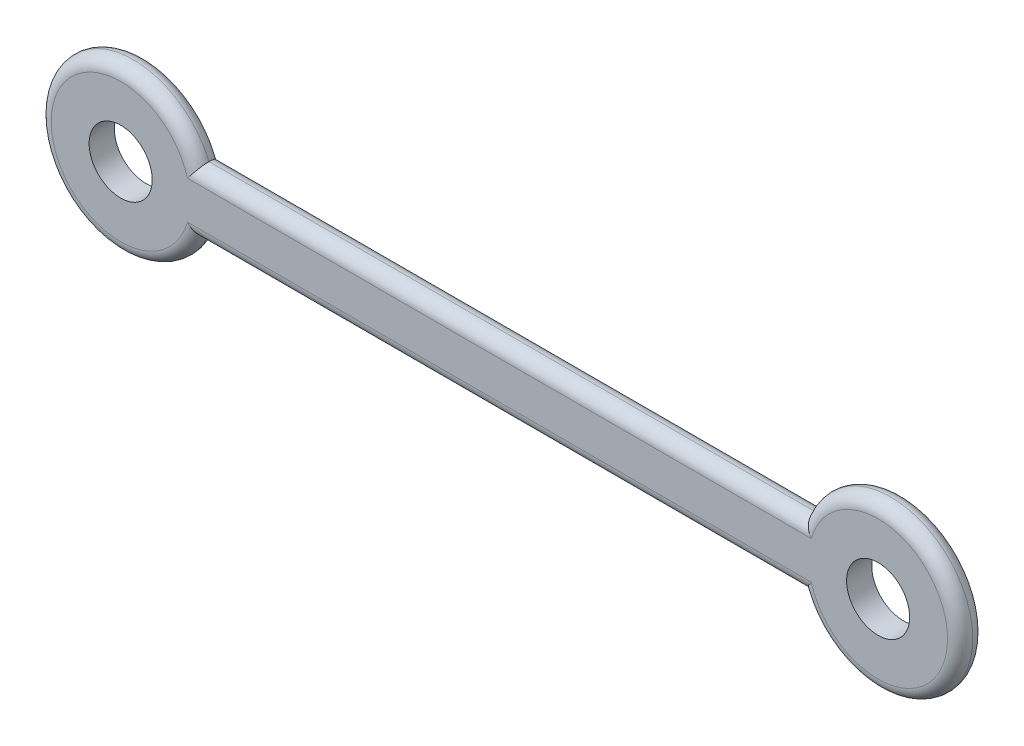
SolidWorks part; units mm, degrees
ref_plane "Front Plane" through (0, 0, 0) normal (0, 0, 1) x (1, 0, 0)
ref_plane "Top Plane" through (0, 0, 0) normal (0, 1, 0) x (1, 0, 0)
ref_plane "Right Plane" through (0, 0, 0) normal (1, 0, 0) x (0, 0, -1)
sketch "Sketch1" plane through (0, 0, 0) normal (0, 0, 1) x (1, 0, 0)
  line L1 (15.24, -6.35) -> (137.16, -6.35)
  line L2 (15.24, 6.35) -> (137.16, 6.35)
  circle A0 centre (0, 0) radius 6.35
  arc A1 (15.24, 6.35) -> (15.24, -6.35) centre (0, 0) ccw
  circle A2 centre (152.4, 0) radius 6.35
  arc A3 (137.16, -6.35) -> (137.16, 6.35) centre (152.4, 0) ccw
  dimension "D1" = 12.7
  dimension "D2" = 33.02
  dimension "D4" = 33.02
  dimension "D5" = 12.7
  dimension "D3" = 152.4
extrude "Boss-Extrude1" add sketch "Sketch1" along normal blind 5.08
fillet "Fillet1" radius 2.54 4 edges at (-16.51, 0, 5.08) (76.2, -6.35, 5.08) (76.2, 6.35, 5.08) (168.91, 0, 5.08)
fillet "Fillet2" radius 2.54 4 edges at (76.2, -6.35, 0) (-16.51, 0, 0) (76.2, 6.35, 0) (168.91, 0, 0)
